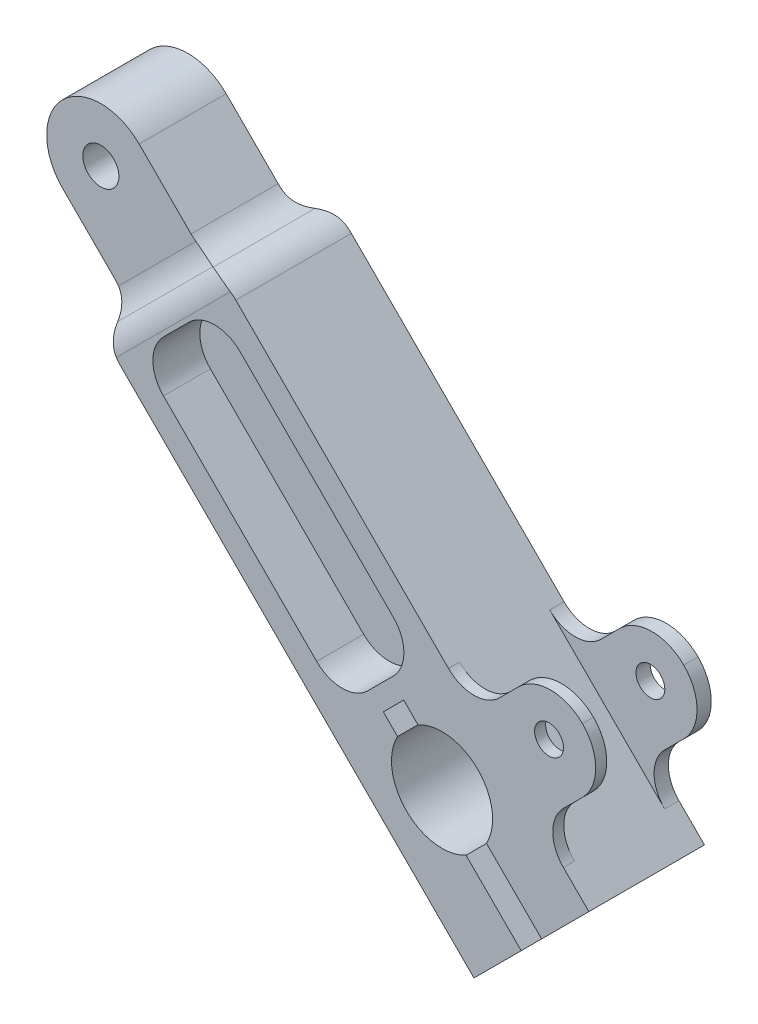
SolidWorks part; units mm, degrees
material "6061-T6 (SS)"
ref_plane "Front Plane" through (0, 0, 0) normal (0, 0, 1) x (1, 0, 0)
ref_plane "Top Plane" through (0, 0, 0) normal (0, 1, 0) x (1, 0, 0)
ref_plane "Right Plane" through (0, 0, 0) normal (1, 0, 0) x (0, 0, -1)
sketch "Sketch2" plane through (0, 0, 0) normal (0, 0, 1) x (1, 0, 0)
  line L0 (0, 0) -> (-234.0257, 0) construction
  line L1 (0, 0) -> (132.15, 132.15) construction
  line L2 (0, 0) -> (130.2279, -130.2279) construction
  line L3 (-10.6066, -10.6066) -> (10.6066, 10.6066) construction
  line L4 (-10.6066, -10.6066) -> (21.2132, -42.4264) construction
  line L5 (21.2132, -42.4264) -> (42.4264, -21.2132) construction
  line L6 (42.4264, -21.2132) -> (10.6066, 10.6066) construction
  line L7 (0, -21.2132) -> (21.2132, 0)
  line L9 (21.2132, 0) -> (53.033, -31.8198)
  line L10 (0, -21.2132) -> (31.8198, -53.033)
  line L11 (31.8198, -53.033) -> (26.5165, -58.3363)
  line L12 (114.318, -146.1378) -> (26.5165, -58.3363)
  line L13 (53.033, -31.8198) -> (58.3363, -26.5165)
  line L14 (128.4601, -96.6403) -> (58.3363, -26.5165)
  line L15 (146.1378, -114.318) -> (167.351, -93.1047)
  line L16 (167.351, -93.1047) -> (149.6733, -75.4271)
  line L17 (149.6733, -75.4271) -> (128.4601, -96.6403)
  line L18 (158.5121, -84.2659) -> (119.6213, -119.6213) construction
  line L19 (146.1378, -114.318) -> (160.2799, -128.4601)
  line L20 (114.318, -146.1378) -> (128.4601, -160.2799)
  line L21 (160.2799, -128.4601) -> (147.1984, -141.5416)
  line L22 (109.0147, -103.3578) -> (112.9628, -107.306)
  line L23 (103.3578, -109.0147) -> (109.0147, -103.3578)
  line L24 (103.3578, -109.0147) -> (107.306, -112.9628)
  line L25 (131.9365, -126.2797) -> (147.1984, -141.5416)
  line L26 (126.2797, -131.9365) -> (141.5416, -147.1984)
  line L27 (141.5416, -147.1984) -> (128.4601, -160.2799)
  line L28 (31.8198, -53.033) -> (53.033, -31.8198)
  line L29 (128.4601, -96.6403) -> (146.1378, -114.318)
  circle A0 centre (21.2132, -21.2132) radius 5
  circle A1 centre (149.2524, -92.6839) radius 4
  arc A2 (107.306, -112.9628) -> (126.2797, -131.9365) centre (119.6213, -119.6213) ccw
  arc A3 (131.9365, -126.2797) -> (112.9628, -107.306) centre (119.6213, -119.6213) ccw
  point P8 (0, 0)
  point P15 (10.6066, -10.6066)
  point P18 (130.2279, -130.2279)
  point P35 (111.5259, -126.9806)
  point P40 (106.1862, -106.1862)
  dimension "D4" = 10
  dimension "D5" = 15
  dimension "D12" = 8
  dimension "D13" = 12.5
  dimension "D14" = 28
  dimension "D1" = 184.17
  dimension "D2" = 30
  dimension "D3" = 45
  dimension "D6" = 15
  dimension "D7" = 30
  dimension "D8" = 45
  dimension "D9" = 45
  dimension "D10" = 30
  dimension "D11" = 25
  dimension "D15" = 20
  dimension "D17" = 19
extrude "Boss-Extrude1" add sketch "Sketch2" along normal blind 38 contours A3 L25 L21 L19 L29 L14 L13 L28 L11 L12 L20 L27 L26 A2 L24 L23 L22 region at (89.1363, -89.1363, 0)
extrude "Boss-Extrude2" add sketch "Sketch2<3>" along normal blind 6.5 contours L17 L29 L15 L16 A1 region at (139.4556, -86.4226, 0)
sketch "Sketch2<3>" plane through (0, 0, 0) normal (0, 0, 1) x (1, 0, 0) same geometry as "Sketch2"
fillet "Fillet1" radius 12.5 2 edges at (167.351, -93.1047, 3.25) (149.6733, -75.4271, 3.25)
ref_plane "Plane1" through (0, 0, 19) normal (0, 0, -1) x (-1, 0, 0)
mirror "Mirror1" about plane through (0, 0, 19) normal (0, 0, -1) of "Boss-Extrude2", "Fillet1"
sketch "Sketch3" plane through (42.4264, -42.4264, 0) normal (-0.7071, 0.7071, 0) x (0, 0, 1)
  line L0 (19, 73.5699) -> (19, -73.5699) construction
  line L1 (6.5, 15) -> (31.5, 15)
  line L2 (6.5, 15) -> (6.5, -15)
  line L3 (6.5, -15) -> (31.5, -15)
  line L4 (31.5, 15) -> (31.5, -15)
  line L5 (6.5, 15) -> (31.5, -15) construction
  line L6 (6.5, -15) -> (31.5, 15) construction
  point P0 (19, 0)
  dimension "D1" = 30
  dimension "D2" = 25
extrude "Boss-Extrude3" add sketch "Sketch3" along normal blind 45
sketch "Sketch4" plane through (0, 0, 31.5) normal (0, 0, 1) x (1, 0, 0)
  line L0 (10.6066, -10.6066) -> (31.8198, -31.8198) construction
  line L1 (0, -21.2132) -> (21.2132, 0) construction
  circle A0 centre (21.2132, -21.2132) radius 5
  dimension "D1" = 10
  dimension "D2" = 15
extrude "Cut-Extrude1" cut sketch "Sketch4" against normal through all
sketch "Sketch12" plane through (0, 0, 31.5) normal (0, 0, 1) x (1, 0, 0)
  line L4 (31.8198, -53.033) -> (53.033, -31.8198)
  line L5 (53.033, -31.8198) -> (21.2132, 0)
  line L6 (21.2132, 0) -> (0, -21.2132)
  line L7 (0, -21.2132) -> (31.8198, -53.033)
  line L8 (31.8198, -53.033) -> (53.033, -31.8198)
  line L9 (53.033, -31.8198) -> (21.2132, 0)
  line L10 (21.2132, 0) -> (0, -21.2132)
  line L11 (0, -21.2132) -> (31.8198, -53.033)
  dimension "D1" = 0
extrude "Cut-Extrude8" cut sketch "Sketch12" against normal up to surface (0.897 mm away)
fillet "Fillet2" radius 15 2 edges at (21.2132, 0, 18.5515) (0, -21.2132, 18.5515)
sketch "Sketch5" plane through (144.37, -144.37, 0) normal (0.7071, -0.7071, 0) x (0, 0, -1)
  line L0 (-38, -13.25) -> (0, -13.25) construction
  line L1 (-38, -4) -> (-38, -22.5) construction
  line L2 (0, -4) -> (0, -22.5) construction
  circle A0 centre (-27, -13.25) radius 4
  circle A1 centre (-13, -13.25) radius 4
  dimension "D1" = 8
  dimension "D2" = 8
  dimension "D3" = 14
  dimension "D4" = 11
fillet "Fillet3" radius 10 4 edges at (128.4601, -96.6403, 34.75) (128.4601, -96.6403, 3.25) (146.1378, -114.318, 34.75) (146.1378, -114.318, 3.25)
sketch "Sketch8" plane through (-15.9099, -15.9099, 0) normal (-0.7071, -0.7071, 0) x (0, 0, 1)
  circle A4 centre (20.5915, -151.019) radius 4 construction
  circle A5 centre (20.5915, -192.17) radius 4 construction
  circle A6 centre (20.5915, -151.019) radius 4
  circle A7 centre (20.5915, -192.17) radius 4
extrude "Cut-Extrude4" cut sketch "Sketch8" against normal blind 10
sketch "Sketch9" plane through (0, 0, 0) normal (0, 0, -1) x (-1, 0, 0)
  line L0 (-128.4601, -160.2799) -> (-26.5165, -58.3363)
  line L1 (-128.4601, -160.2799) -> (-184.1342, -104.6058)
  line L2 (-26.5165, -58.3363) -> (-82.1906, -2.6622)
  line L3 (-184.1342, -104.6058) -> (-82.1906, -2.6622)
extrude "Cut-Extrude5" cut sketch "Sketch9" against normal up to surface (2.5515 mm away) contours L0 L1 L3 L2
sketch "Sketch10" plane through (0, 0, 38) normal (0, 0, 1) x (1, 0, 0)
  line L0 (128.4601, -160.2799) -> (26.5165, -58.3363)
  line L1 (128.4601, -160.2799) -> (184.01, -104.73)
  line L2 (26.5165, -58.3363) -> (82.0664, -2.7864)
  line L3 (184.01, -104.73) -> (82.0664, -2.7864)
extrude "Cut-Extrude6" cut sketch "Sketch10" against normal up to surface (3.4485 mm away)
sketch "Sketch11" plane through (0, 0, 2.5515) normal (0, 0, -1) x (-1, 0, 0)
  line L0 (-106.1862, -106.1862) -> (-42.4264, -42.4264)
  line L1 (-103.3578, -109.0147) -> (-109.0147, -103.3578) construction
  line L2 (-26.5165, -58.3363) -> (-58.3363, -26.5165) construction
  line L3 (-88.4485, -109.6617) -> (-109.6617, -88.4485)
  line L4 (-88.4485, -109.6617) -> (-38.951, -60.1642)
  line L5 (-109.6617, -88.4485) -> (-60.1642, -38.951)
  line L6 (-38.951, -60.1642) -> (-60.1642, -38.951)
  line L7 (-88.4485, -109.6617) -> (-60.1642, -38.951) construction
  line L8 (-109.6617, -88.4485) -> (-38.951, -60.1642) construction
  line L9 (-88.4485, -109.6617) -> (-109.6617, -88.4485)
  line L10 (-88.4485, -109.6617) -> (-91.984, -113.1972)
  line L11 (-109.6617, -88.4485) -> (-113.1972, -91.984)
  line L12 (-91.984, -113.1972) -> (-113.1972, -91.984)
  line L13 (-74.3063, -74.3063) -> (-63.6997, -84.9129)
  line L14 (-38.951, -60.1642) -> (-60.1642, -38.951)
  line L15 (-38.951, -60.1642) -> (-35.4154, -56.6286)
  line L16 (-60.1642, -38.951) -> (-56.6286, -35.4154)
  line L17 (-35.4154, -56.6286) -> (-56.6286, -35.4154)
  point P7 (-74.3063, -74.3063)
  dimension "D1" = 70
  dimension "D2" = 30
  dimension "D3" = 5
  dimension "D4" = 90
  dimension "D5" = 5
extrude "Cut-Extrude7" cut sketch "Sketch11" against normal blind 13 contours L4 L6 L0 L3 | L0 L6 L5 L3 | L12 L0 L3 L11 | L12 L10 L3 L0 | L13 L0 L3 L4 | L14 L15 L17 L16 region at (106.1261, -95.5195, 2.5515) region at (95.5195, -106.1261, 2.5515) region at (79.6096, -69.003, 2.5515) region at (81.3774, -91.984, 2.5515) region at (56.6286, -67.2352, 2.5515)
fillet "Fillet4" radius 10 4 edges at (91.984, -113.1972, 9.0515) (113.1972, -91.984, 9.0515) (35.4154, -56.6286, 9.0515) (56.6286, -35.4154, 9.0515)
fillet "Fillet6" radius 10 4 edges at (31.8198, -53.033, 18.5515) (53.033, -31.8198, 18.5515) (42.4264, -42.4264, 6.5) (42.4264, -42.4264, 30.603)
fillet "Fillet7" radius 10 4 edges at (58.3363, -26.5165, 18.5515) (26.5165, -58.3363, 18.5515) (42.4264, -42.4264, 2.5515) (42.4264, -42.4264, 34.5515)
ref_plane "Plane2" through (0, 0, 18.5515) normal (0, 0, -1) x (-1, 0, 0)
mirror "Mirror2" about plane through (0, 0, 18.5515) normal (0, 0, -1) of "Fillet4", "Cut-Extrude7"
thread "Thread1" pitch 1 method cut profile "Thread Profile2" start angle 0, offset 0, length 10, pitch 1, diameter 8
ref_plane "Plane4" through (122.8032, -154.623, 20.5915) normal (0, 0, 1) x (0.7071, -0.7071, 0)
sketch "Thread Profile2" plane through (122.8032, -154.623, 20.5915) normal (0, 0, 1) x (0.7071, -0.7071, 0)
  line L0 (0, 0) -> (0, 1) construction
  line L1 (0, 0) -> (0.5413, 0.3125)
  line L2 (0.5413, 0.3125) -> (0.5413, 0.4375)
  line L3 (0.5413, 0.4375) -> (0, 0.75)
  line L4 (0.5413, 0.375) -> (0, 0.375) construction
  line L11 (0, 0) -> (0, 0.75)
  point P2 (0, 0)
  dimension "Pitch" = 1
  dimension "Profile_Angle" = 60
  dimension "Profile_Land" = 0.125
  dimension "Profile_Height" = 0.5413
thread "Thread2" pitch 1 method cut profile "Thread Profile3" start angle 0, offset 0, length 10, pitch 1, diameter 8
ref_plane "Plane5" through (93.7051, -125.5249, 20.5915) normal (0, 0, 1) x (0.7071, -0.7071, 0)
sketch "Thread Profile3" plane through (93.7051, -125.5249, 20.5915) normal (0, 0, 1) x (0.7071, -0.7071, 0)
  line L0 (0, 0) -> (0, 1) construction
  line L1 (0, 0) -> (0.5413, 0.3125)
  line L2 (0.5413, 0.3125) -> (0.5413, 0.4375)
  line L3 (0.5413, 0.4375) -> (0, 0.75)
  line L4 (0.5413, 0.375) -> (0, 0.375) construction
  line L11 (0, 0) -> (0, 0.75)
  point P2 (0, 0)
  dimension "Pitch" = 1
  dimension "Profile_Angle" = 60
  dimension "Profile_Land" = 0.125
  dimension "Profile_Height" = 0.5413
